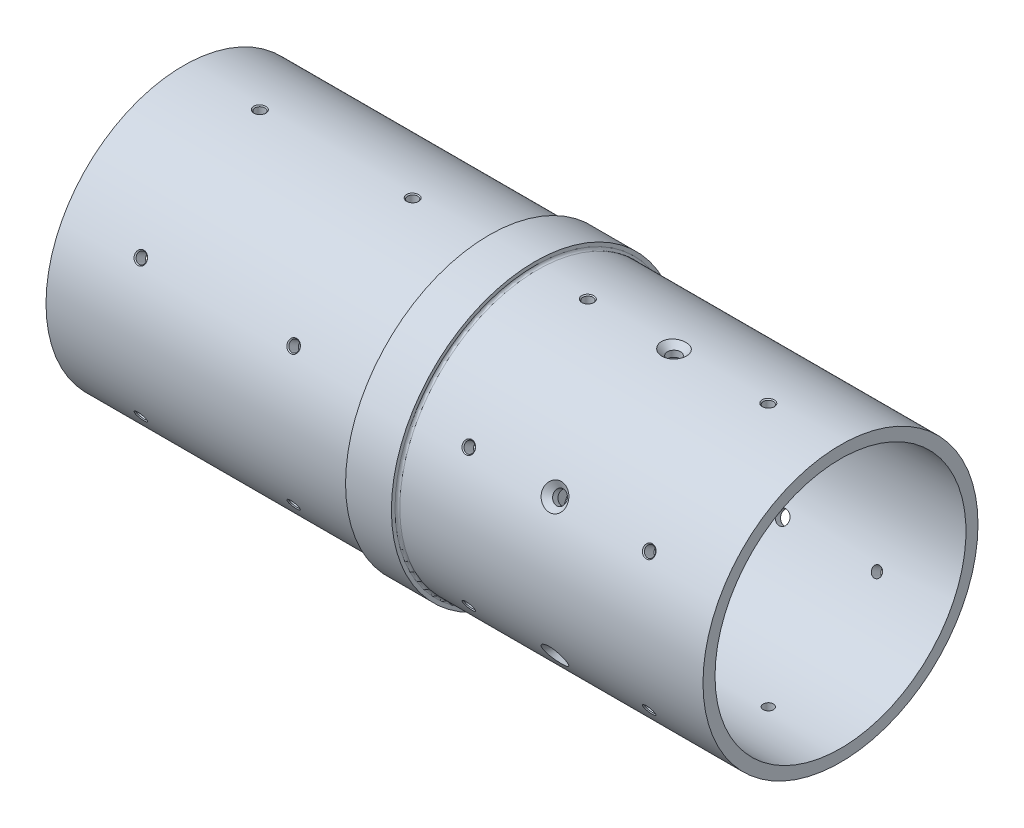
SolidWorks part; units mm, degrees
ref_plane "Front Plane" through (0, 0, 0) normal (0, 0, 1) x (1, 0, 0)
ref_plane "Top Plane" through (0, 0, 0) normal (0, 1, 0) x (1, 0, 0)
ref_plane "Right Plane" through (0, 0, 0) normal (1, 0, 0) x (0, 0, -1)
sketch "Sketch1" plane through (0, 0, 0) normal (0, 1, 0) x (1, 0, 0)
  line L0 (-95.7, 42.15) -> (-105.7, 52.15)
  line L1 (0, -55) -> (0, 55) construction
  line L2 (0, 52.15) -> (-74.2, 52.15)
  line L3 (-76.2, 50.15) -> (-76.2, 42.15)
  line L4 (-76.2, 42.15) -> (-95.7, 42.15)
  line L7 (-273.05, 52.15) -> (-273.05, 57.15)
  line L8 (-273.05, 57.15) -> (-147.05, 57.15)
  line L9 (-146.05, 58.15) -> (-146.05, 59.65)
  line L10 (-146.05, 59.65) -> (-127, 59.65)
  line L11 (-127, 59.65) -> (-127, 58.15)
  line L12 (-126, 57.15) -> (0, 57.15)
  line L13 (0, 57.15) -> (0, 52.15)
  line L14 (-105.7, 52.15) -> (-273.05, 52.15)
  arc A0 (-74.2, 52.15) -> (-76.2, 50.15) centre (-74.2, 50.15) ccw
  arc A2 (-147.05, 57.15) -> (-146.05, 58.15) centre (-147.05, 58.15) ccw
  arc A3 (-127, 58.15) -> (-126, 57.15) centre (-126, 58.15) ccw
  point P18 (-76.2, 52.15)
  point P21 (-95.7, 52.15)
  point P24 (-146.05, 57.15)
  point P27 (-127, 57.15)
  dimension "D11" = 2
  dimension "D13" = 1
  dimension "D1" = 127
  dimension "D2" = 127
  dimension "D3" = 5
  dimension "D4" = 19.05
  dimension "D5" = 76.2
  dimension "D6" = 10
  dimension "D7" = 19.5
  dimension "D8" = 10
  dimension "D9" = 5
  dimension "D10" = 2.5
sketch "Sketch3" plane through (0, 0, 0) normal (0, 1, 0) x (1, 0, 0)
  line L0 (-185.7686, 0) -> (-52.5722, 0)
  line L1 (-150.1775, 0) -> (150.1775, 0) construction
revolve "Revolve1" add sketch "Sketch1" angle 360 about L0
ref_plane "Plane1" through (0, 57.15, 0) normal (0, 1, 0) x (1, 0, 0)
hole_wizard "CSK for M5 Flat Head Machine Screw2" positions "Sketch6" profile "Sketch5" countersink size "M5" standard "ANSI Metric"
sketch "Sketch6" plane through (0, 57.15, 0) normal (0, 1, 0) x (1, 0, 0)
  line L0 (-65.615, 0) -> (65.615, 0) construction
  line L1 (-69.2, 0) -> (0, 0)
  point P0 (-69.2, 0)
  dimension "D1" = 69.2
sketch "Sketch5" plane through (-69.2, 57.15, 0) normal (1, 0, 0) x (0, 0, 1)
  line L0 (0, 0) -> (0, 13.6524)
  line L1 (0, 13.6524) -> (2.75, 12)
  line L2 (2.75, 12) -> (2.75, 2.45)
  line L3 (2.75, 2.45) -> (5.2, 0)
  line L5 (5.2, 0) -> (0, 0)
  line L6 (-2.75, 2.45) -> (-5.2, 0) construction
  line L10 (0, 13.6524) -> (-2.75, 12) construction
  line L11 (0, -6.35) -> (0, 107.95) construction
  dimension "Hole Dia." = 5.5
  dimension "Hole Depth" = 12
  dimension "Near C'Sink Dia." = 10.4
  dimension "Near C'Sink Angle" = 90
  dimension "Drill Angle" = 118
pattern_circular "CirPattern1" count 6 over 360 of "CSK for M5 Flat Head Machine Screw2" reverse direction yes
hole_wizard "M5x0.8 Tapped Hole1" positions "Sketch7" profile "Sketch8" tap size "M5x0.8" standard "ANSI Metric"
sketch "Sketch7" plane through (0, 57.15, 0) normal (0, 1, 0) x (1, 0, 0)
  line L0 (-65.615, 0) -> (65.615, 0) construction
  line L1 (-30, 0) -> (0, 0)
  line L2 (-105, 0) -> (0, 0)
  point P0 (-30, 0)
  point P9 (-105, 0)
  dimension "D1" = 30
  dimension "D2" = 105
sketch "Sketch8" plane through (-30, 57.15, 0) normal (1, 0, 0) x (0, 0, 1)
  line L0 (0, 0) -> (0, 9.2618)
  line L1 (0, 9.2618) -> (2.1, 8)
  line L2 (2.1, 8) -> (2.1, 0.425)
  line L3 (2.1, 0.425) -> (2.525, 0)
  line L5 (2.525, 0) -> (0, 0)
  line L6 (-2.1, 0.425) -> (-2.525, 0) construction
  line L10 (0, 9.2618) -> (-2.1, 8) construction
  line L11 (0, -6.35) -> (0, 107.95) construction
  dimension "Tap Drill Dia." = 4.2
  dimension "Tap Drill Depth" = 8
  dimension "Near C'Sink Dia." = 5.05
  dimension "Near C'Sink Angle" = 90
  dimension "Drill Angle" = 118
cosmetic thread "Hole Thread1" parameters "D1"=5, "D2"=5
cosmetic thread "Hole Thread2" parameters "D1"=5, "D2"=5
pattern_circular "CirPattern2" count 6 over 360 of "M5x0.8 Tapped Hole1" reverse direction yes
cosmetic thread "Hole Thread3" parameters "D1"=5, "D2"=5
cosmetic thread "Hole Thread4" parameters "D1"=5, "D2"=5
cosmetic thread "Hole Thread5" parameters "D1"=5, "D2"=5
cosmetic thread "Hole Thread6" parameters "D1"=5, "D2"=5
cosmetic thread "Hole Thread7" parameters "D1"=5, "D2"=5
cosmetic thread "Hole Thread8" parameters "D1"=5, "D2"=5
cosmetic thread "Hole Thread9" parameters "D1"=5, "D2"=5
cosmetic thread "Hole Thread10" parameters "D1"=5, "D2"=5
cosmetic thread "Hole Thread11" parameters "D1"=5, "D2"=5
cosmetic thread "Hole Thread12" parameters "D1"=5, "D2"=5
ref_plane "Plane2" through (0, 57.15, 0) normal (0, 1, 0) x (1, 0, 0)
hole_wizard "M5x0.8 Tapped Hole2" positions "Sketch9" profile "Sketch10" tap size "M5x0.8" standard "ANSI Metric"
sketch "Sketch9" plane through (0, 57.15, 0) normal (0, 1, 0) x (1, 0, 0)
  line L0 (-65.615, 0) -> (65.615, 0) construction
  line L1 (-241.3, 0) -> (-273.05, 0)
  line L2 (-273.05, 57.15) -> (-273.05, -57.15) construction
  line L4 (-177.8, 0) -> (-273.05, 0)
  point P0 (-241.3, 0)
  point P4 (-177.8, 0)
  dimension "D1" = 31.75
  dimension "D2" = 95.25
sketch "Sketch10" plane through (-241.3, 57.15, 0) normal (1, 0, 0) x (0, 0, 1)
  line L0 (0, 0) -> (0, 9.2618)
  line L1 (0, 9.2618) -> (2.1, 8)
  line L2 (2.1, 8) -> (2.1, 0.425)
  line L3 (2.1, 0.425) -> (2.525, 0)
  line L5 (2.525, 0) -> (0, 0)
  line L6 (-2.1, 0.425) -> (-2.525, 0) construction
  line L10 (0, 9.2618) -> (-2.1, 8) construction
  line L11 (0, -6.35) -> (0, 107.95) construction
  dimension "Tap Drill Dia." = 4.2
  dimension "Tap Drill Depth" = 8
  dimension "Near C'Sink Dia." = 5.05
  dimension "Near C'Sink Angle" = 90
  dimension "Drill Angle" = 118
cosmetic thread "Hole Thread13" parameters "D1"=5.0423, "D2"=5
cosmetic thread "Hole Thread14" parameters "D1"=5.0423, "D2"=5
pattern_circular "CirPattern3" count 6 over 360 of "M5x0.8 Tapped Hole2" reverse direction yes
cosmetic thread "Hole Thread15" parameters "D1"=5.0423, "D2"=5
cosmetic thread "Hole Thread16" parameters "D1"=5.0423, "D2"=5
cosmetic thread "Hole Thread17" parameters "D1"=5.0423, "D2"=5
cosmetic thread "Hole Thread18" parameters "D1"=5.0423, "D2"=5
cosmetic thread "Hole Thread19" parameters "D1"=5.0423, "D2"=5
cosmetic thread "Hole Thread20" parameters "D1"=5.0423, "D2"=5
cosmetic thread "Hole Thread21" parameters "D1"=5.0423, "D2"=5
cosmetic thread "Hole Thread22" parameters "D1"=5.0423, "D2"=5
cosmetic thread "Hole Thread23" parameters "D1"=5.0423, "D2"=5
cosmetic thread "Hole Thread24" parameters "D1"=5.0423, "D2"=5
